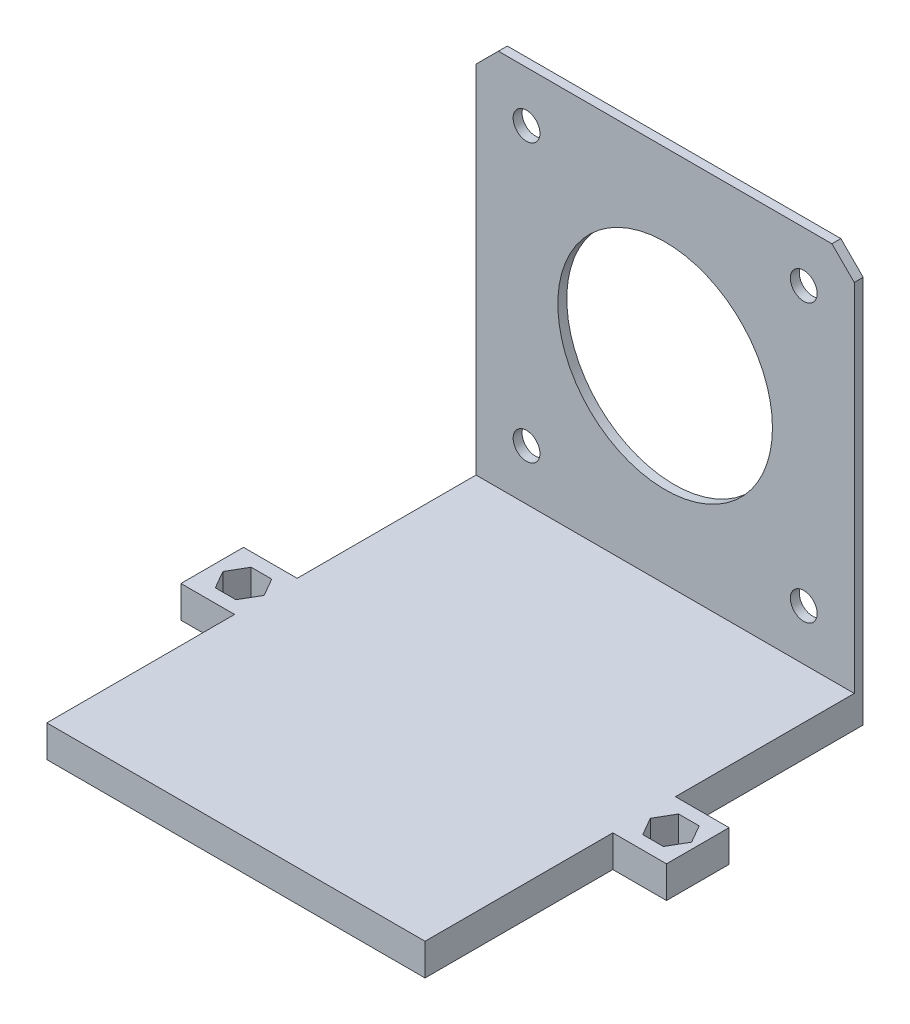
SolidWorks part; units mm, degrees
ref_plane "Alzado" through (0, 0, 0) normal (0, 0, 1) x (1, 0, 0)
ref_plane "Planta" through (0, 0, 0) normal (0, 1, 0) x (1, 0, 0)
ref_plane "Vista lateral" through (0, 0, 0) normal (1, 0, 0) x (0, 0, -1)
sketch "Sketch1" plane through (0, 0, 0) normal (0, 0, 1) x (1, 0, 0)
  line L1 (-25.8145, 17.8273) -> (16.4855, 17.8273)
  line L2 (-25.8145, 17.8273) -> (-25.8145, -24.4727)
  line L3 (-25.8145, -24.4727) -> (16.4855, -24.4727)
  line L4 (16.4855, 17.8273) -> (16.4855, -24.4727)
  dimension "D1" = 42.3
  dimension "D2" = 42.3
extrude "Boss-Extrude1" add sketch "Sketch1" along normal blind 1
sketch "Sketch3" plane through (0, 0, 1) normal (0, 0, 1) x (1, 0, 0)
  line L0 (-25.8145, -24.4727) -> (16.4855, -24.4727) construction
  line L1 (-25.8145, 17.8273) -> (-25.8145, -24.4727) construction
  circle A0 centre (-20.1645, -18.8227) radius 0.5
  circle A1 centre (10.8355, -18.8227) radius 0.5
  circle A2 centre (10.8355, 12.1773) radius 0.5
  circle A3 centre (-20.1645, 12.1773) radius 0.5
  dimension "D1" = 5.65
  dimension "D3" = 31
  dimension "D4" = 31
  dimension "D5" = 31
  dimension "D2" = 5.65
extrude "Cut-Extrude1" cut sketch "Sketch3" against normal through all
chamfer "Chamfer1" distance 2.5 angle 45 4 edges at (-25.8145, -24.4727, 0.5) (16.4855, -24.4727, 0.5) (16.4855, 17.8273, 0.5) (-25.8145, 17.8273, 0.5)
sketch "Sketch4" plane through (0, 0, 1) normal (0, 0, 1) x (1, 0, 0)
  circle A0 centre (-4.6645, -3.3227) radius 12
extrude "Cut-Extrude2" cut sketch "Sketch4" against normal through all
sketch "Sketch5" plane through (0, 0, 1) normal (0, 0, 1) x (1, 0, 0)
  circle A0 centre (-20.1645, 12.1773) radius 1.5
  circle A1 centre (-20.1645, -18.8227) radius 1.5
  circle A2 centre (10.8355, -18.8227) radius 1.5
  circle A3 centre (10.8355, 12.1773) radius 1.5
extrude "Cut-Extrude3" cut sketch "Sketch5" against normal through all
sketch "Sketch6" plane through (0, -24.4727, 0) normal (0, -1, 0) x (1, 0, 0)
  line L1 (-25.8145, 1) -> (16.4855, 1)
  line L2 (-25.8145, 1) -> (-25.8145, 0)
  line L3 (-25.8145, 0) -> (16.4855, 0)
  line L4 (16.4855, 1) -> (16.4855, 0)
extrude "Boss-Extrude2" add sketch "Sketch6" along normal blind 3.21
sketch "Sketch7" plane through (0, 0, 1) normal (0, 0, 1) x (1, 0, 0)
  line L1 (-25.8145, -21.9727) -> (16.4855, -21.9727)
  line L2 (-25.8145, -21.9727) -> (-25.8145, -27.6827)
  line L3 (-25.8145, -27.6827) -> (16.4855, -27.6827)
  line L4 (16.4855, -21.9727) -> (16.4855, -27.6827)
extrude "Boss-Extrude3" add sketch "Sketch7" against normal blind 1
sketch "Sketch8" plane through (0, -27.6827, 0) normal (0, -1, 0) x (1, 0, 0)
  line L1 (-25.8145, 1) -> (16.4855, 1)
  line L2 (-25.8145, 1) -> (-25.8145, 0)
  line L3 (-25.8145, 0) -> (16.4855, 0)
  line L4 (16.4855, 1) -> (16.4855, 0)
extrude "Boss-Extrude4" add sketch "Sketch8" along normal blind 0.35
sketch "Sketch9" plane through (0, 0, 1) normal (0, 0, 1) x (1, 0, 0)
  line L5 (-25.8145, -28.0327) -> (-25.8145, -25.4727) construction
  line L6 (-25.8145, 15.3273) -> (-25.8145, -28.0327) construction
  line L7 (16.4855, -28.0327) -> (16.4855, 15.3273) construction
  line L8 (-25.8145, -25.4727) -> (16.4855, -25.4727)
  line L9 (-25.8145, -25.4727) -> (-25.8145, -24.4727)
  line L10 (-25.8145, -24.4727) -> (16.4855, -24.4727)
  line L11 (16.4855, -25.4727) -> (16.4855, -24.4727)
  dimension "D1" = 2.56
  dimension "D2" = 1
extrude "Boss-Extrude5" add sketch "Sketch9" along normal blind 48
sketch "Sketch10" plane through (0, -25.4727, 0) normal (0, -1, 0) x (1, 0, 0)
  line L0 (16.4855, 49) -> (16.4855, 1) construction
  line L1 (-25.8145, 49) -> (16.4855, 49)
  line L2 (-25.8145, 49) -> (-25.8145, 48)
  line L3 (-25.8145, 48) -> (16.4855, 48)
  line L4 (16.4855, 49) -> (16.4855, 48)
  dimension "D1" = 1
extrude "Boss-Extrude6" add sketch "Sketch10" along normal blind 2.56
sketch "Sketch11" plane through (-25.8145, 0, 0) normal (-1, 0, 0) x (0, 0, 1)
  line L1 (0, -28.0327) -> (49, -28.0327)
  line L2 (0, -28.0327) -> (0, -24.4727)
  line L3 (0, -24.4727) -> (49, -24.4727)
  line L4 (49, -28.0327) -> (49, -24.4727)
extrude "Boss-Extrude7" add sketch "Sketch11" against normal blind 1
sketch "Sketch12" plane through (-25.8145, 0, 0) normal (-1, 0, 0) x (0, 0, 1)
  line L0 (49, -28.0327) -> (0, -28.0327) construction
  line L1 (22, -28.0327) -> (27, -28.0327)
  line L2 (22, -28.0327) -> (22, -27.0327)
  line L3 (22, -27.0327) -> (27, -27.0327)
  line L4 (27, -28.0327) -> (27, -27.0327)
  dimension "D1" = 1
  dimension "D2" = 5
  dimension "D3" = 22
extrude "Boss-Extrude8" add sketch "Sketch12" along normal blind 5
sketch "Sketch13" plane through (16.4855, 0, 0) normal (1, 0, 0) x (0, 0, -1)
  line L1 (-49, -24.4727) -> (0, -24.4727)
  line L2 (-49, -24.4727) -> (-49, -28.0327)
  line L3 (-49, -28.0327) -> (0, -28.0327)
  line L4 (0, -24.4727) -> (0, -28.0327)
extrude "Boss-Extrude9" add sketch "Sketch13" against normal blind 1
sketch "Sketch14" plane through (0, -24.4727, 0) normal (0, 1, 0) x (1, 0, 0)
  line L0 (-25.8145, -27) -> (16.4855, -27) construction
  line L1 (16.4855, -49) -> (16.4855, -1) construction
  line L3 (16.4855, -27) -> (21.4855, -27)
  line L4 (16.4855, -27) -> (16.4855, -22)
  line L5 (16.4855, -22) -> (21.4855, -22)
  line L6 (21.4855, -27) -> (21.4855, -22)
  dimension "D1" = 5
  dimension "D2" = 5
extrude "Boss-Extrude10" add sketch "Sketch14" against normal up to vertex (3.56 mm away) up to point (-30.8145, -28.0327, 27)
sketch "Sketch15" plane through (21.4855, 0, 0) normal (1, 0, 0) x (0, 0, -1)
  line L0 (-27, -28.0327) -> (-27, -24.4727) construction
  line L1 (-22, -24.4727) -> (-27, -24.4727)
  line L2 (-22, -24.4727) -> (-22, -27.0327)
  line L3 (-22, -27.0327) -> (-27, -27.0327)
  line L4 (-27, -24.4727) -> (-27, -27.0327)
  point P7 (0, 0)
  dimension "D1" = 1
extrude "Cut-Extrude4" cut sketch "Sketch15" against normal blind 5
sketch "Sketch16" plane through (0, -27.0327, 0) normal (0, 1, 0) x (1, 0, 0)
  circle A0 centre (-28.3145, -24.5) radius 1
  circle A1 centre (18.9855, -24.5) radius 1
extrude "Cut-Extrude5" cut sketch "Sketch16" against normal blind 5
sketch "Sketch17" plane through (0, -27.0327, 0) normal (0, 1, 0) x (1, 0, 0)
  line L1 (-30.8145, -27) -> (-25.8145, -27)
  line L2 (-30.8145, -27) -> (-30.8145, -22)
  line L3 (-30.8145, -22) -> (-25.8145, -22)
  line L4 (-25.8145, -27) -> (-25.8145, -22)
  circle A0 centre (-28.3145, -24.5) radius 1
extrude "Boss-Extrude11" add sketch "Sketch17" along normal up to vertex (2.56 mm away) up to point (-25.8145, -24.4727, 49)
sketch "Sketch19" plane through (0, -24.4727, 0) normal (0, 1, 0) x (1, 0, 0)
  line L1 (-29.4692, -26.5) -> (-27.1598, -26.5)
  line L2 (-27.1598, -26.5) -> (-26.0051, -24.5)
  line L3 (-26.0051, -24.5) -> (-27.1598, -22.5)
  line L4 (-27.1598, -22.5) -> (-29.4692, -22.5)
  line L5 (-29.4692, -22.5) -> (-30.6239, -24.5)
  line L6 (-30.6239, -24.5) -> (-29.4692, -26.5)
  circle A0 centre (-28.3145, -24.5) radius 2 construction
extrude "Cut-Extrude6" cut sketch "Sketch19" against normal blind 5
sketch "Sketch20" plane through (-30.8145, 0, 0) normal (-1, 0, 0) x (0, 0, 1)
  line L1 (27, -24.4727) -> (22, -24.4727)
  line L2 (27, -24.4727) -> (27, -28.0327)
  line L3 (27, -28.0327) -> (22, -28.0327)
  line L4 (22, -24.4727) -> (22, -28.0327)
extrude "Boss-Extrude12" add sketch "Sketch20" along normal blind 1
sketch "Sketch21" plane through (0, 0, 27) normal (0, 0, 1) x (1, 0, 0)
  line L1 (-25.8145, -24.4727) -> (-31.8145, -24.4727)
  line L2 (-25.8145, -24.4727) -> (-25.8145, -28.0327)
  line L3 (-25.8145, -28.0327) -> (-31.8145, -28.0327)
  line L4 (-31.8145, -24.4727) -> (-31.8145, -28.0327)
extrude "Boss-Extrude13" add sketch "Sketch21" along normal blind 1
sketch "Sketch22" plane through (0, 0, 22) normal (0, 0, -1) x (-1, 0, 0)
  line L1 (31.8145, -24.4727) -> (25.8145, -24.4727)
  line L2 (31.8145, -24.4727) -> (31.8145, -28.0327)
  line L3 (31.8145, -28.0327) -> (25.8145, -28.0327)
  line L4 (25.8145, -24.4727) -> (25.8145, -28.0327)
extrude "Boss-Extrude14" add sketch "Sketch22" along normal blind 1
sketch "Sketch23" plane through (0, -27.0327, 0) normal (0, 1, 0) x (1, 0, 0)
  line L1 (21.4855, -27) -> (16.4855, -27)
  line L2 (21.4855, -27) -> (21.4855, -22)
  line L3 (21.4855, -22) -> (16.4855, -22)
  line L4 (16.4855, -27) -> (16.4855, -22)
extrude "Boss-Extrude15" add sketch "Sketch23" along normal up to vertex (2.56 mm away) up to point (16.4855, -24.4727, 49)
sketch "Sketch24" plane through (0, 0, 27) normal (0, 0, 1) x (1, 0, 0)
  line L1 (21.4855, -24.4727) -> (16.4855, -24.4727)
  line L2 (21.4855, -24.4727) -> (21.4855, -28.0327)
  line L3 (21.4855, -28.0327) -> (16.4855, -28.0327)
  line L4 (16.4855, -24.4727) -> (16.4855, -28.0327)
extrude "Boss-Extrude16" add sketch "Sketch24" along normal blind 1
sketch "Sketch25" plane through (0, 0, 22) normal (0, 0, -1) x (-1, 0, 0)
  line L1 (-21.4855, -24.4727) -> (-16.4855, -24.4727)
  line L2 (-21.4855, -24.4727) -> (-21.4855, -28.0327)
  line L3 (-21.4855, -28.0327) -> (-16.4855, -28.0327)
  line L4 (-16.4855, -24.4727) -> (-16.4855, -28.0327)
extrude "Boss-Extrude17" add sketch "Sketch25" along normal blind 1
sketch "Sketch26" plane through (21.4855, 0, 0) normal (1, 0, 0) x (0, 0, -1)
  line L1 (-28, -24.4727) -> (-21, -24.4727)
  line L2 (-28, -24.4727) -> (-28, -28.0327)
  line L3 (-28, -28.0327) -> (-21, -28.0327)
  line L4 (-21, -24.4727) -> (-21, -28.0327)
extrude "Boss-Extrude18" add sketch "Sketch26" along normal blind 1
sketch "Sketch29" plane through (0, -24.4727, 0) normal (0, 1, 0) x (1, 0, 0)
  line L0 (22.4855, -24.5) -> (19.4855, -24.5) construction
  line L1 (22.4855, -21) -> (22.4855, -28) construction
  line L3 (20.6402, -26.5) -> (21.7949, -24.5)
  line L4 (21.7949, -24.5) -> (20.6402, -22.5)
  line L5 (20.6402, -22.5) -> (18.3308, -22.5)
  line L6 (18.3308, -22.5) -> (17.1761, -24.5)
  line L7 (17.1761, -24.5) -> (18.3308, -26.5)
  line L8 (18.3308, -26.5) -> (20.6402, -26.5)
  circle A0 centre (19.4855, -24.5) radius 2 construction
extrude "Cut-Extrude7" cut sketch "Sketch29" against normal blind 21
